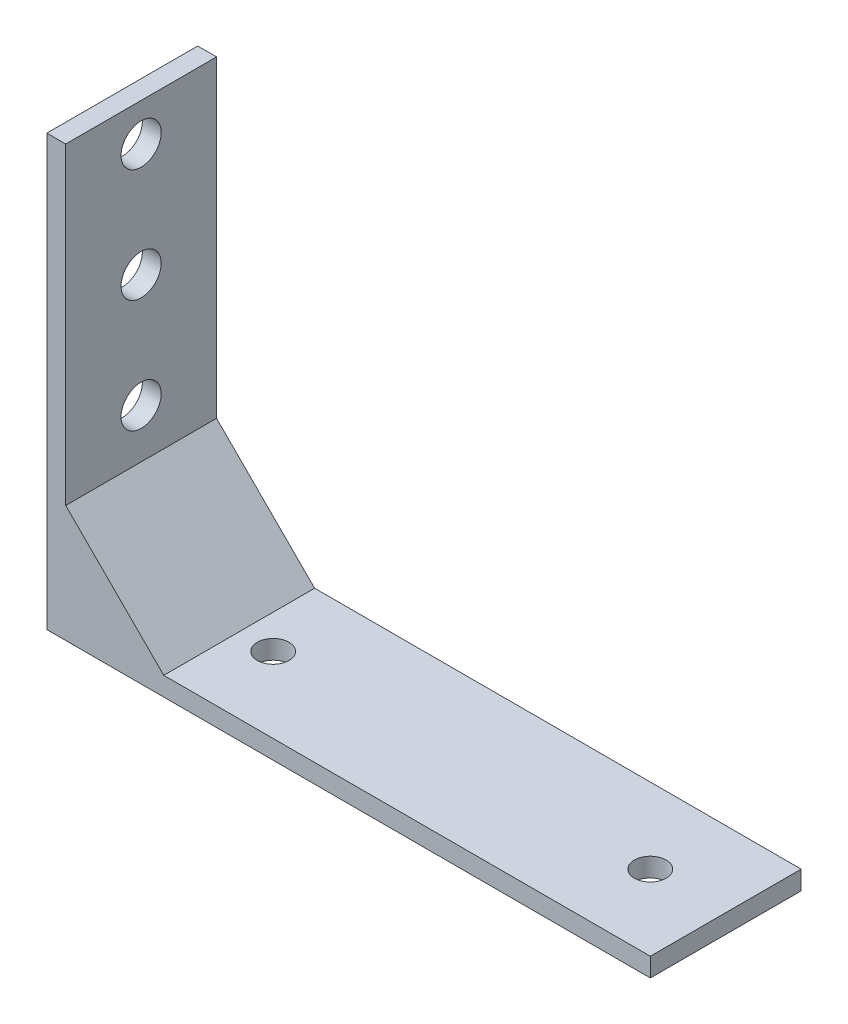
SolidWorks part; units mm, degrees
ref_plane "Front Plane" through (0, 0, 0) normal (0, 0, 1) x (1, 0, 0)
ref_plane "Top Plane" through (0, 0, 0) normal (0, 1, 0) x (1, 0, 0)
ref_plane "Right Plane" through (0, 0, 0) normal (1, 0, 0) x (0, 0, -1)
sketch "Sketch1" plane through (0, 0, 0) normal (0, 0, 1) x (1, 0, 0)
  line L1 (0, 0) -> (3.175, 0)
  line L2 (0, 0) -> (0, 72.39)
  line L3 (0, 72.39) -> (3.175, 72.39)
  line L4 (3.175, 3.175) -> (3.175, 72.39)
  line L5 (0, 0) -> (101.6, 0)
  line L6 (0, 0) -> (0, 3.175)
  line L7 (3.175, 3.175) -> (101.6, 3.175)
  line L8 (101.6, 0) -> (101.6, 3.175)
  dimension "D1" = 101.6
  dimension "D2" = 3.175
  dimension "D3" = 3.175
  dimension "D4" = 72.39
extrude "Boss-Extrude1" add sketch "Sketch1" along normal blind 25.4 contours L5 L8 L7 L4 L3 L2 L1 region at (1.2475, 1.5875, 0)
sketch "Sketch2" plane through (0, 3.175, 0) normal (0, 1, 0) x (1, 0, 0)
  line L0 (101.6, -25.4) -> (101.6, 0) construction
  line L1 (3.175, -25.4) -> (101.6, -25.4) construction
  circle A0 centre (88.9, -12.7) radius 2.667
  circle A1 centre (25.4, -12.7) radius 2.667
  dimension "D5" = 5.334
  dimension "D6" = 5.334
  dimension "D2" = 63.5
  dimension "D1" = 12.7
  dimension "D3" = 12.7
  dimension "D4" = 12.7
extrude "Cut-Extrude1" cut sketch "Sketch2" against normal blind 25.4
sketch "Sketch3" plane through (0, 0, 0) normal (-1, 0, 0) x (0, 0, 1)
  line L0 (25.4, 0) -> (0, 0) construction
  line L2 (0, 3.175) -> (0, 72.39) construction
  circle A0 centre (12.7, 27.94) radius 3.3782
  circle A1 centre (12.7, 46.99) radius 3.3782
  circle A2 centre (12.7, 66.04) radius 3.3782
  dimension "D1" = 6.7564
  dimension "D2" = 6.7564
  dimension "D3" = 6.7564
  dimension "D4" = 27.94
  dimension "D5" = 19.05
  dimension "D6" = 19.05
  dimension "D7" = 12.7
  dimension "D8" = 12.7
  dimension "D9" = 12.7
extrude "Cut-Extrude2" cut sketch "Sketch3" against normal through all
sketch "Sketch4" plane through (0, 0, 25.4) normal (0, 0, 1) x (1, 0, 0)
  line L0 (3.175, 19.685) -> (19.685, 3.175)
  line L1 (3.175, 3.175) -> (3.175, 72.39) construction
  line L2 (3.175, 3.175) -> (101.6, 3.175) construction
  line L3 (19.685, 3.175) -> (3.175, 3.175)
  line L4 (3.175, 3.175) -> (3.175, 19.685)
  dimension "D1" = 45
  dimension "D2" = 16.51
extrude "Boss-Extrude2" add sketch "Sketch4" against normal blind 25.4
